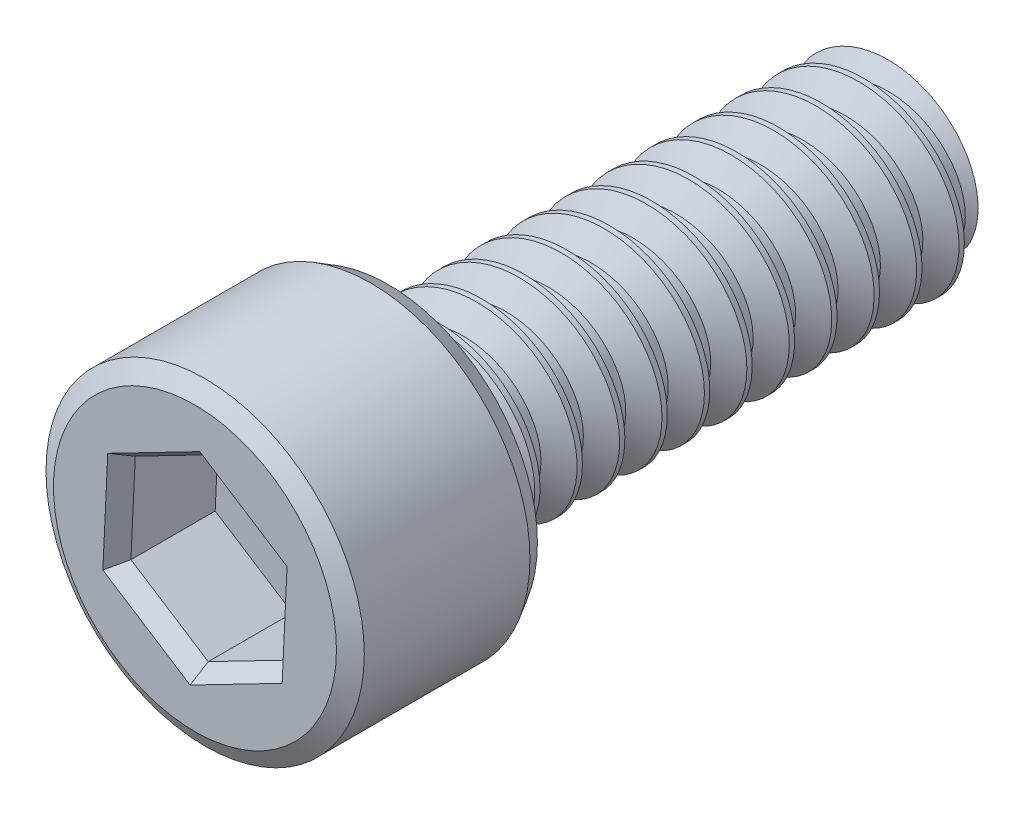
SolidWorks part; units mm, degrees
ref_plane "Front Plane" through (0, 0, 0) normal (0, 0, 1) x (1, 0, 0)
ref_plane "Top Plane" through (0, 0, 0) normal (0, 1, 0) x (1, 0, 0)
ref_plane "Right Plane" through (0, 0, 0) normal (1, 0, 0) x (0, 0, -1)
sketch "Sketch1" plane through (0, 0, 0) normal (0, 0, 1) x (1, 0, 0)
  circle A0 centre (0, 0) radius 3.9688
  dimension "D1" = 7.9375
extrude "Boss-Extrude1" add sketch "Sketch1" along normal blind 4.826
sketch "Sketch2" plane through (0, 0, 4.826) normal (0, 0, 1) x (1, 0, 0)
  line L1 (1.9282, -1.2378) -> (2.0361, 1.051)
  line L2 (2.0361, 1.051) -> (0.1079, 2.2888)
  line L3 (0.1079, 2.2888) -> (-1.9282, 1.2378)
  line L4 (-1.9282, 1.2378) -> (-2.0361, -1.051)
  line L5 (-2.0361, -1.051) -> (-0.1079, -2.2888)
  line L6 (-0.1079, -2.2888) -> (1.9282, -1.2378)
  circle A0 centre (0, 0) radius 1.9844 construction
  circle A1 centre (0, 0) radius 3.9688 construction
  dimension "D1" = 3.9688
  dimension "D2" = 0.1079
extrude "Cut-Extrude1" cut sketch "Sketch2" against normal blind 2.54
sketch "Sketch3" plane through (0, 0, 0) normal (0, 0, -1) x (-1, 0, 0)
  circle A0 centre (0, 0) radius 2.413
  dimension "D1" = 4.826
extrude "Boss-Extrude2" add sketch "Sketch3" along normal blind 12.7
chamfer "Chamfer2" distance 0.254 angle 60 9 edges at (3.9688, 0, 0) (3.9688, 0, 4.826) (-0.9102, 1.7633, 4.826) (1.072, 1.6699, 4.826) (1.9822, -0.0934, 4.826) (0.9102, -1.7633, 4.826) (-1.072, -1.6699, 4.826) (-1.9822, 0.0934, 4.826) (-2.413, 0, -12.7)
thread "Thread1" pitch 1.0583 start angle 0, offset 2.54, length 0, pitch 1.0583, diameter 4.826
ref_plane "Plane1" through (2.413, 0, -14.986) normal (0, -1, 0) x (1, 0, 0)
sketch "Thread Profile1" plane through (2.413, 0, -14.986) normal (0, -1, 0) x (1, 0, 0)
  line L0 (0, 0) -> (0, 1.0583) construction
  line L11 (0, 0) -> (0, 0.926)
  line L12 (0, 0.926) -> (-0.5728, 0.5953)
  line L13 (-0.5728, 0.5953) -> (-0.5728, 0.3307)
  line L15 (-0.5728, 0.3307) -> (0, 0)
  line L17 (-0.5728, 0.463) -> (0, 0.463) construction
  point P2 (0, 0)
  dimension "Pitch" = 1.0583
  dimension "Profile_Angle" = 60
  dimension "Profile_Land" = 0.2646
  dimension "Profile_Height" = 0.5728
